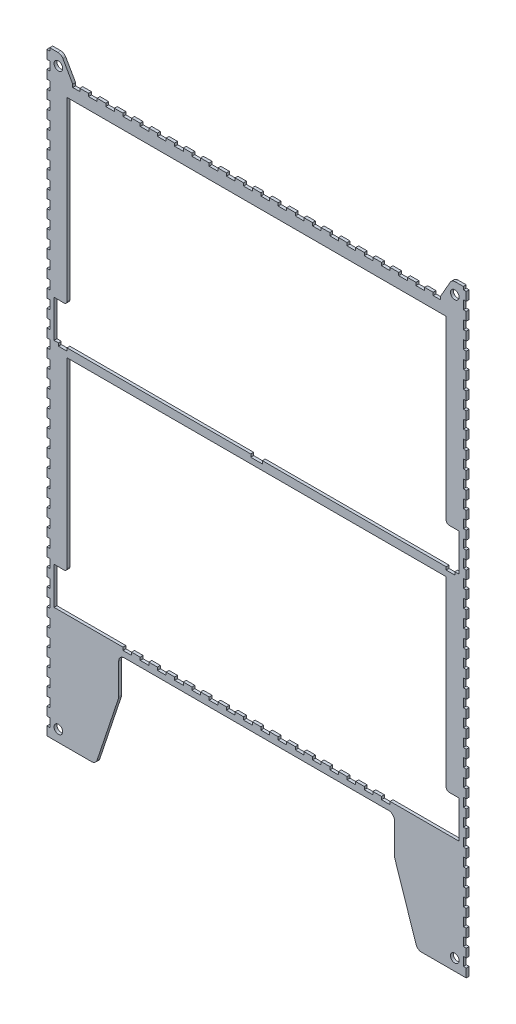
SolidWorks part; units mm, degrees
material "ABS"
ref_plane "Front Plane" through (0, 0, 0) normal (0, 0, 1) x (1, 0, 0)
ref_plane "Top Plane" through (0, 0, 0) normal (0, 1, 0) x (1, 0, 0)
ref_plane "Right Plane" through (0, 0, 0) normal (1, 0, 0) x (0, 0, -1)
sketch "Sketch1" plane through (0, 0, 0) normal (0, 0, 1) x (1, 0, 0)
  line L1 (-114.3, -127) -> (114.3, -127)
  line L2 (-114.3, -127) -> (-114.3, 127)
  line L3 (-114.3, 127) -> (114.3, 127)
  line L4 (114.3, -127) -> (114.3, 127)
  line L5 (-114.3, -127) -> (114.3, 127) construction
  line L6 (-114.3, 127) -> (114.3, -127) construction
  point P0 (0, 0)
  dimension "D1" = 254
  dimension "D2" = 228.6
extrude "Boss-Extrude1" add sketch "Sketch1" along normal mid plane 1.5875
sketch "Sketch2" plane through (0, 0, 0.7937) normal (0, 0, 1) x (1, 0, 0)
  line L0 (-114.3, -127) -> (-114.3, -190.5)
  line L1 (-114.3, -190.5) -> (-88.9, -190.5)
  line L2 (-88.9, -190.5) -> (-76.2, -152.4)
  line L3 (-76.2, -152.4) -> (-76.2, -127)
  line L4 (-114.3, -127) -> (114.3, -127) construction
  line L5 (-76.2, -127) -> (-114.3, -127)
  line L6 (114.3, -127) -> (114.3, -190.5)
  line L7 (114.3, -190.5) -> (88.9, -190.5)
  line L8 (88.9, -190.5) -> (76.2, -152.4)
  line L9 (76.2, -152.4) -> (76.2, -127)
  line L10 (114.3, -127) -> (76.2, -127)
  line L11 (-114.3, 127) -> (-114.3, 139.7)
  line L12 (-114.3, 139.7) -> (-107.95, 139.7)
  line L13 (-107.95, 139.7) -> (-101.6, 128.5875)
  line L14 (114.3, 127) -> (-114.3, 127) construction
  line L15 (-101.6, 127) -> (-114.3, 127)
  line L16 (114.3, 127) -> (114.3, 139.7)
  line L17 (114.3, 139.7) -> (107.95, 139.7)
  line L18 (-101.6, 128.5875) -> (-101.6, 127)
  line L19 (101.6, 127) -> (114.3, 127)
  line L20 (107.95, 139.7) -> (101.6, 128.5875)
  line L21 (101.6, 128.5875) -> (101.6, 127)
  dimension "D1" = 63.5
  dimension "D2" = 25.4
  dimension "D3" = 25.4
  dimension "D4" = 38.1
  dimension "D5" = 12.7
  dimension "D6" = 6.35
  dimension "D7" = 12.7
  dimension "D8" = 1.5875
extrude "Boss-Extrude2" add sketch "Sketch2" against normal up to surface (1.5875 mm away) up to face at (0, 0, -0.7937)
sketch "Sketch4" plane through (0, 0, 0.7937) normal (0, 0, 1) x (1, 0, 0)
  line L0 (-114.3, 139.7) -> (-114.3, -190.5) construction
  line L1 (-114.3, 138.1125) -> (-115.8875, 138.1125)
  line L2 (-114.3, 138.1125) -> (-114.3, 133.35)
  line L3 (-114.3, 133.35) -> (-115.8875, 133.35)
  line L4 (-115.8875, 138.1125) -> (-115.8875, 133.35)
  line L5 (-107.95, 139.7) -> (-114.3, 139.7) construction
  dimension "D1" = 4.7625
  dimension "D2" = 1.5875
  dimension "D3" = 1.5875
extrude "Boss-Extrude3" add sketch "Sketch4" against normal up to surface (1.5875 mm away) up to face at (1.5875, -16.5199, -0.7937)
pattern_linear "LPattern1" count 35 spacing 9.525 along (0, -1, 0) of "Boss-Extrude3"
mirror "Mirror1" about plane through (0, 0, 0) normal (1, 0, 0) of "LPattern1"
sketch "Sketch5" plane through (0, 0, 0.7937) normal (0, 0, 1) x (1, 0, 0)
  line L0 (101.6, 127) -> (-101.6, 127) construction
  line L1 (-97.6312, 127) -> (-92.8688, 127)
  line L2 (-97.6312, 127) -> (-97.6313, 128.5875)
  line L3 (-97.6313, 128.5875) -> (-92.8688, 128.5875)
  line L4 (-92.8688, 127) -> (-92.8688, 128.5875)
  line L6 (-101.6, 127) -> (-101.6, 128.5875) construction
  dimension "D1" = 4.7625
  dimension "D2" = 1.5875
  dimension "D3" = 3.9688
extrude "Boss-Extrude4" add sketch "Sketch5" against normal up to surface (1.5875 mm away) up to face at (0.087, -23.4129, -0.7937)
pattern_linear "LPattern2" count 21 spacing 9.525 along (1, 0, 0) of "Boss-Extrude4"
mirror "Mirror2" about plane through (0, 0, 0) normal (0, 1, 0) of "LPattern2"
sketch "Sketch3" plane through (0, 0, 0.7937) normal (0, 0, 1) x (1, 0, 0)
  line L0 (0, 120.65) -> (0, -120.65) construction
  line L1 (-104.775, -120.65) -> (104.775, -120.65)
  line L2 (-104.775, -120.65) -> (-104.775, 120.65)
  line L3 (-104.775, 120.65) -> (104.775, 120.65)
  line L4 (104.775, -120.65) -> (104.775, 120.65)
  point P7 (0, 0)
  dimension "D1" = 209.55
  dimension "D2" = 241.3
extrude "Cut-Extrude1" cut sketch "Sketch3" against normal through all
sketch "Sketch10" plane through (0, 0, 0.7937) normal (0, 0, 1) x (1, 0, 0)
  line L0 (76.2, -128.5875) -> (76.2, -152.4) construction
  line L1 (-76.2, -128.5875) -> (76.2, -128.5875)
  line L2 (-76.2, -128.5875) -> (-76.2, -131.7625)
  line L3 (-76.2, -131.7625) -> (76.2, -131.7625)
  line L4 (76.2, -128.5875) -> (76.2, -131.7625)
  dimension "D1" = 3.175
extrude "Boss-Extrude7" add sketch "Sketch10" against normal up to surface (1.5875 mm away) up to face at (0, 0, -0.7937)
sketch "Sketch6" plane through (0, 0, 0.7937) normal (0, 0, 1) x (1, 0, 0)
  line L1 (111.9187, 21.4312) -> (-111.9188, 21.4312)
  line L2 (111.9187, 21.4312) -> (111.9187, 0.7937)
  line L3 (111.9187, 0.7937) -> (-111.9188, 0.7937)
  line L4 (-111.9188, 21.4312) -> (-111.9188, 0.7937)
  line L5 (111.9187, 21.4312) -> (-111.9188, 0.7937) construction
  line L6 (111.9187, 0.7937) -> (-111.9188, 21.4312) construction
  line L7 (-111.9188, -127) -> (111.9188, -127)
  line L8 (-111.9188, -127) -> (-111.9188, -106.3625)
  line L9 (-111.9188, -106.3625) -> (111.9188, -106.3625)
  line L10 (111.9188, -127) -> (111.9188, -106.3625)
  line L11 (-111.9188, -127) -> (111.9188, -106.3625) construction
  line L12 (-111.9188, -106.3625) -> (111.9188, -127) construction
  point P0 (0, 11.1125)
  point P5 (0, -116.6813)
  dimension "D1" = 20.6375
  dimension "D2" = 0.7937
  dimension "D3" = 223.8375
  dimension "D4" = 127
  dimension "D5" = 20.6375
extrude "Cut-Extrude2" cut sketch "Sketch6" against normal up to surface (1.5875 mm away) contours L7 L10 L9 L8 | L1 L4 L3 L2 region at (0, 11.1125, 0.7937) region at (0, -116.6812, 0.7937) up to face at (0.1372, 10.3483, -0.7937)
fillet "Fillet1" radius 1.5875 4 edges at (-104.775, 21.4312, 0) (104.775, 21.4312, 0) (104.775, -106.3625, 0) (-104.775, -106.3625, 0)
sketch "Sketch8" plane through (0, 0, 0.7937) normal (0, 0, 1) x (1, 0, 0)
  line L0 (115.8875, 0) -> (114.3, 0) construction
  line L1 (-104.775, 0.7937) -> (-109.5375, 0.7937)
  line L2 (-104.775, 0.7937) -> (-104.775, -0.7938)
  line L3 (-104.775, -0.7938) -> (-109.5375, -0.7938)
  line L4 (-109.5375, 0.7937) -> (-109.5375, -0.7938)
  line L5 (104.775, 0.7937) -> (109.5375, 0.7937)
  line L6 (104.775, 0.7937) -> (104.775, -0.7938)
  line L7 (104.775, -0.7938) -> (109.5375, -0.7938)
  line L8 (109.5375, 0.7937) -> (109.5375, -0.7938)
  line L9 (115.8875, 4.7625) -> (115.8875, 0) construction
extrude "Cut-Extrude3" cut sketch "Sketch8" against normal through all
sketch "Sketch9" plane through (0, 0, 0.7937) normal (0, 0, 1) x (1, 0, 0)
  line L0 (-104.775, -0.7938) -> (-104.775, -104.775) construction
  line L1 (-104.775, -0.7938) -> (104.775, -0.7938)
  line L2 (-104.775, -0.7938) -> (-104.775, -3.9688)
  line L3 (-104.775, -3.9688) -> (104.775, -3.9688)
  line L4 (104.775, -0.7938) -> (104.775, -3.9688)
  line L5 (104.775, -104.775) -> (104.775, -0.7938) construction
  line L7 (104.775, -0.7938) -> (3.175, -0.7938)
  line L8 (104.775, -0.7938) -> (104.775, 0.7937)
  line L9 (104.775, 0.7937) -> (3.175, 0.7937)
  line L10 (3.175, -0.7938) -> (3.175, 0.7937)
  line L11 (-3.175, 0.7937) -> (-104.775, 0.7937)
  line L12 (-3.175, 0.7937) -> (-3.175, -0.7938)
  line L13 (-3.175, -0.7938) -> (-104.775, -0.7938)
  line L14 (-104.775, 0.7937) -> (-104.775, -0.7938)
  dimension "D1" = 3.175
  dimension "D2" = 1.5875
  dimension "D3" = 3.175
  dimension "D4" = 3.175
extrude "Boss-Extrude6" add sketch "Sketch9" against normal up to surface (1.5875 mm away) contours L4 L1 L2 L3 | L11 L14 L1 L12 | L10 L1 L8 L9 region at (-53.975, 0, 0.7937) region at (0, -2.3813, 0.7937) region at (53.975, 0, 0.7937) up to face at (0, -98.8188, -0.7938)
sketch "Sketch11" plane through (0, 0, 0.7937) normal (0, 0, 1) x (1, 0, 0)
  line L0 (-107.95, 139.7) -> (-114.3, 139.7) construction
  line L1 (-109.5375, -184.15) -> (109.5375, -184.15) construction
  line L2 (-109.5375, -184.15) -> (-109.5375, 133.35) construction
  line L3 (-109.5375, 133.35) -> (109.5375, 133.35) construction
  line L4 (109.5375, -184.15) -> (109.5375, 133.35) construction
  line L5 (-109.5375, -184.15) -> (109.5375, 133.35) construction
  line L6 (-109.5375, 133.35) -> (109.5375, -184.15) construction
  line L7 (-115.8875, -190.5) -> (-88.9, -190.5) construction
  circle A0 centre (-109.5375, 133.35) radius 2.3813
  circle A1 centre (-109.5375, -184.15) radius 2.3813
  circle A2 centre (109.5375, 133.35) radius 2.3813
  circle A3 centre (109.5375, -184.15) radius 2.3813
  point P0 (0, -25.4)
  dimension "D2" = 4.7625
  dimension "D1" = 4.7625
  dimension "D3" = 6.35
  dimension "D4" = 6.35
extrude "Cut-Extrude4" cut sketch "Sketch11" against normal through all
fillet "Fillet3" radius 3.175 6 edges at (76.2, -152.4, 0) (76.2, -131.7625, 0) (-76.2, -152.4, 0) (-76.2, -131.7625, 0) (88.9, -190.5, 0) (-88.9, -190.5, 0)
fillet "Fillet4" radius 3.175 2 edges at (-107.95, 139.7, 0) (107.95, 139.7, 0)
